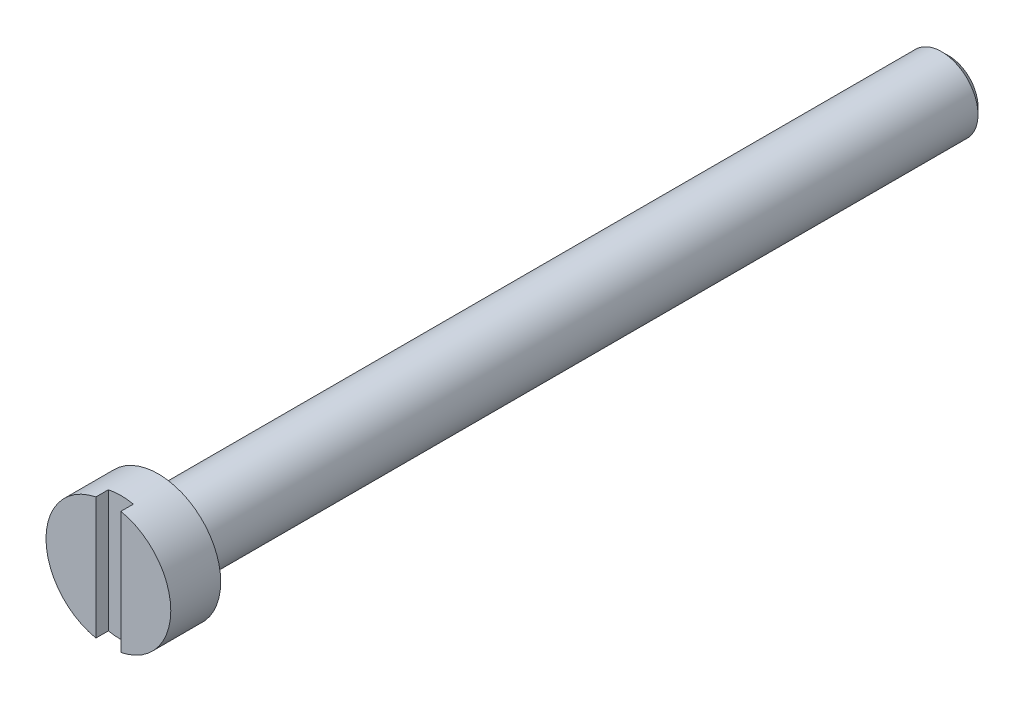
SolidWorks part; units mm, degrees
material "AISI 1020"
ref_plane "Спереди" through (0, 0, 0) normal (0, 0, 1) x (1, 0, 0)
ref_plane "Сверху" through (0, 0, 0) normal (0, 1, 0) x (1, 0, 0)
ref_plane "Справа" through (0, 0, 0) normal (1, 0, 0) x (0, 0, -1)
sketch "Эскиз1" plane through (0, 0, 0) normal (0, 0, 1) x (1, 0, 0)
  circle A0 centre (0, 0) radius 3
  dimension "D1" = 6
extrude "Бобышка-Вытянуть1" add sketch "Эскиз1" along normal blind 2.4
sketch "Эскиз2" plane through (0, 0, 0) normal (0, 0, -1) x (-1, 0, 0)
  circle A0 centre (0, 0) radius 1.75
  dimension "D1" = 3.5
extrude "Бобышка-Вытянуть2" add sketch "Эскиз2" along normal blind 38
cosmetic thread "Условное изображение резьбы1" parameters "D1"=20, "D2"=2.829
chamfer "Фаска1" distance 0.3355 angle 45 1 edges at (-1.75, 0, -38)
sketch "Эскиз3" plane through (0, 0, 0) normal (0, 1, 0) x (1, 0, 0)
  line L0 (-3, -2.4) -> (3, -2.4) construction
  line L1 (-0.6, -1.8) -> (0.6, -1.8)
  line L2 (-0.6, -1.8) -> (-0.6, -3)
  line L3 (-0.6, -3) -> (0.6, -3)
  line L4 (0.6, -1.8) -> (0.6, -3)
  line L5 (-0.6, -1.8) -> (0.6, -3) construction
  line L6 (-0.6, -3) -> (0.6, -1.8) construction
  point P0 (0, -2.4)
  dimension "D1" = 0.6
  dimension "D2" = 1.2
extrude "Вырез-Вытянуть1" cut sketch "Эскиз3" against normal blind 38 and the other way blind 38
